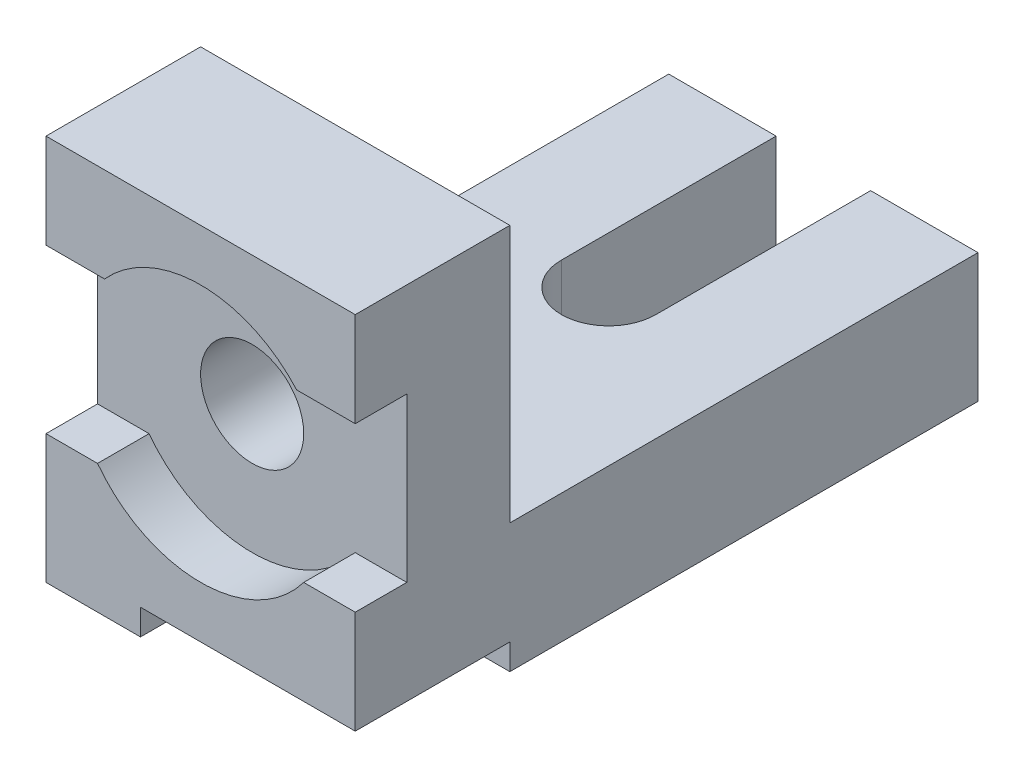
SolidWorks part; units mm, degrees
ref_plane "Front Plane" through (0, 0, 0) normal (0, 0, 1) x (1, 0, 0)
ref_plane "Top Plane" through (0, 0, 0) normal (0, 1, 0) x (1, 0, 0)
ref_plane "Right Plane" through (0, 0, 0) normal (1, 0, 0) x (0, 0, -1)
sketch "Sketch1" plane through (0, 0, 0) normal (0, 0, 1) x (1, 0, 0)
  line L1 (-36, 45) -> (36, 45)
  line L2 (-36, 45) -> (-36, -45)
  line L3 (-36, -45) -> (36, -45)
  line L4 (36, 45) -> (36, -45)
  line L5 (-36, 45) -> (36, -45) construction
  line L6 (-36, -45) -> (36, 45) construction
  line L7 (36, -45) -> (-14, -45)
  line L8 (36, -45) -> (36, -39)
  line L9 (36, -39) -> (-14, -39)
  line L10 (-14, -45) -> (-14, -39)
  line L11 (36, -15) -> (-36, -15)
  line L12 (36, -15) -> (36, -45)
  line L13 (36, -45) -> (-36, -45)
  line L14 (-36, -15) -> (-36, -45)
  line L15 (-36, 45) -> (36, 45)
  line L16 (-36, 45) -> (-36, 23)
  line L17 (-36, 23) -> (36, 23)
  line L18 (36, 45) -> (36, 23)
  circle A2 centre (0, 3) radius 30
  circle A3 centre (0, 3) radius 12
  point P0 (0, 0)
  point P16 (0, 0)
  dimension "D7" = 60
  dimension "D8" = 24
  dimension "D1" = 72
  dimension "D2" = 90
  dimension "D3" = 6
  dimension "D4" = 50
  dimension "D5" = 30
  dimension "D6" = 22
  dimension "D9" = 48
extrude "Boss-Extrude1" add sketch "Sketch1" along normal blind 24 contours L17 A2 L11 A3 | L17 A2 | L11 A2 | A2 L11 L4 L17 | A2 L17 L2 L11 region at (-31.6626, 4.568, 0) region at (31.6626, 4.568, 0) region at (0, 27.0633, 0) region at (0, 22.2898, 0) region at (0, -19.8932, 0)
extrude "Boss-Extrude2" add sketch "Sketch1<4>" along normal blind 36 contours A2 L17 L4 L1 L2 | A2 L11 L2 L3 L10 L9 L4 region at (0, 35.6862, 0) region at (-2.2643, -30.3216, 0)
sketch "Sketch1<4>" plane through (0, 0, 0) normal (0, 0, 1) x (1, 0, 0) same geometry as "Sketch1"
extrude "Boss-Extrude5" add sketch "Sketch1<9>" against normal blind 109 contours L11 A2 | A2 L11 L2 L3 L10 L9 L4 | L8 L9 L10 L7 region at (-2.2643, -30.3216, 0) region at (0, -19.8932, 0)
sketch "Sketch1<9>" plane through (0, 0, 0) normal (0, 0, 1) x (1, 0, 0) same geometry as "Sketch1"
extrude "Boss-Extrude6" add sketch "Sketch1<10>" against normal blind 36 contours L10 L3 L4 L9 region at (11, -42, 0)
sketch "Sketch1<10>" plane through (0, 0, 0) normal (0, 0, 1) x (1, 0, 0) same geometry as "Sketch1"
sketch "Sketch3" plane through (0, -15, 0) normal (0, 1, 0) x (1, 0, 0)
  line L0 (36, 109) -> (-36, 109) construction
  line L1 (11, 109) -> (-11, 109)
  line L2 (11, 109) -> (11, 59)
  line L3 (11, 59) -> (-11, 59)
  line L4 (-11, 109) -> (-11, 59)
  circle A0 centre (0, 59) radius 11
  point P6 (0, 109)
  line M5 (36, 109) -> (-36, 109)
  dimension "D1" = 22
  dimension "D2" = 50
extrude "Cut-Extrude1" cut sketch "Sketch3" against normal up to surface (30 mm away) contours A0 L2 L4 M5 | L3 A0 | L3 A0 region at (0, -15, -88.2468) region at (0, -15, -54.3315) region at (0, -15, -63.6685) up to face at (-4.6667, -45, -24.3333)
